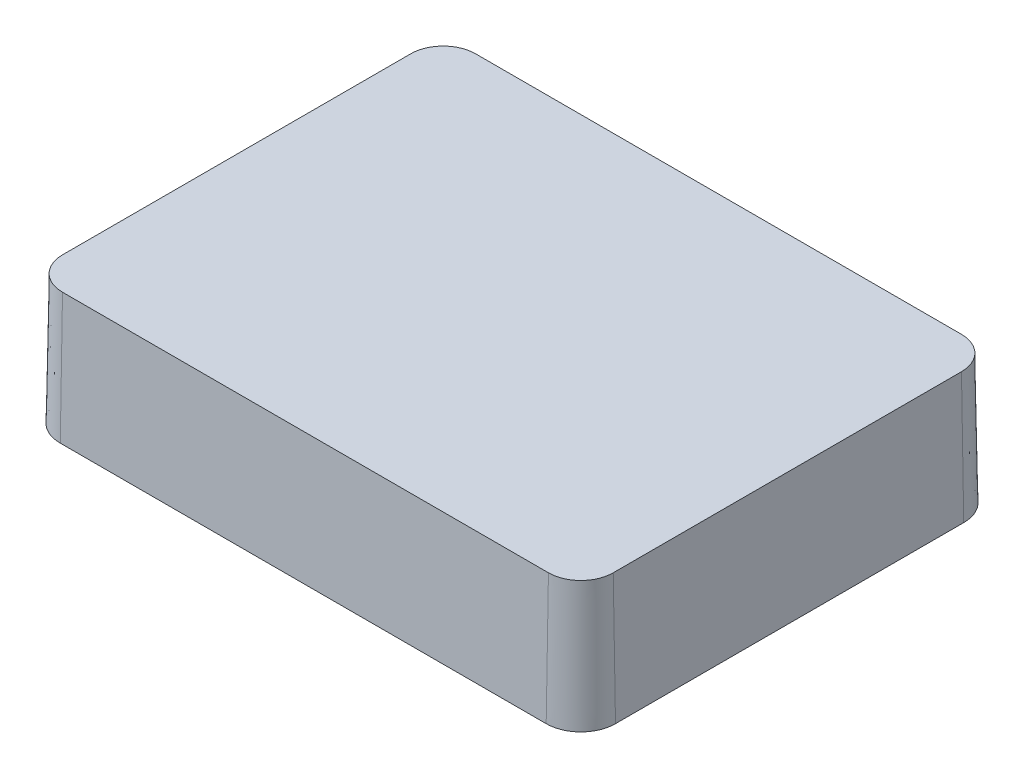
SolidWorks part; units mm, degrees
ref_plane "Front Plane" through (0, 0, 0) normal (0, 0, 1) x (1, 0, 0)
ref_plane "Top Plane" through (0, 0, 0) normal (0, 1, 0) x (1, 0, 0)
ref_plane "Right Plane" through (0, 0, 0) normal (1, 0, 0) x (0, 0, -1)
sketch "Sketch1" plane through (0, 0, 0) normal (0, 1, 0) x (1, 0, 0)
  line L1 (-7.5, -6.375) -> (7.5, -6.375)
  line L2 (-8.5, -5.375) -> (-8.5, 5.375)
  line L3 (-7.5, 6.375) -> (7.5, 6.375)
  line L4 (8.5, -5.375) -> (8.5, 5.375)
  line L5 (-8.5, -6.375) -> (8.5, 6.375) construction
  line L6 (-8.5, 6.375) -> (8.5, -6.375) construction
  arc A0 (-8.5, 5.375) -> (-7.5, 6.375) centre (-7.5, 5.375) cw
  arc A1 (8.5, 5.375) -> (7.5, 6.375) centre (7.5, 5.375) ccw
  arc A2 (8.5, -5.375) -> (7.5, -6.375) centre (7.5, -5.375) cw
  arc A3 (-7.5, -6.375) -> (-8.5, -5.375) centre (-7.5, -5.375) cw
  point P0 (0, 0)
  dimension "D3" = 1
  dimension "D1" = 17
  dimension "D2" = 12.75
extrude "Boss-Extrude1" add sketch "Sketch1" against normal blind 4 draft 1 draft outward yes
shell "Shell1" thickness 0.5 removed face at (0, -4, 0)
sketch "Sketch2" plane through (0, -0.5, 0) normal (0, -1, 0) x (1, 0, 0)
  line L0 (-0.6, 2.9308) -> (-0.6, 0.6)
  line L1 (-2.9308, 0.6) -> (-0.6, 0.6)
  line L2 (0, -2.2) -> (0, 2.2) construction
  line L3 (2.2, 0) -> (-2.2, 0) construction
  line L4 (-2.9308, -0.6) -> (-0.6, -0.6)
  line L5 (0.6, 2.9308) -> (0.6, 0.6)
  line L6 (-0.6, -0.6) -> (-0.6, -2.9308)
  line L7 (0.6, -0.6) -> (0.6, -2.9308)
  line L8 (0.6, -0.6) -> (2.9308, -0.6)
  line L9 (0.6, 0.6) -> (2.9308, 0.6)
  arc A0 (-2.9308, -0.6) -> (-0.6, -2.9308) centre (0, 0) ccw
  arc A1 (2.9308, 0.6) -> (0.6, 2.9308) centre (0, 0) ccw
  arc A2 (-0.6, 2.9308) -> (-2.9308, 0.6) centre (0, 0) ccw
  arc A3 (0.6, -2.9308) -> (2.9308, -0.6) centre (0, 0) ccw
  dimension "D1" = 0.6
  dimension "D2" = 0.6
extrude "Boss-Extrude2" add sketch "Sketch2" along normal blind 5.5 draft 1.5
